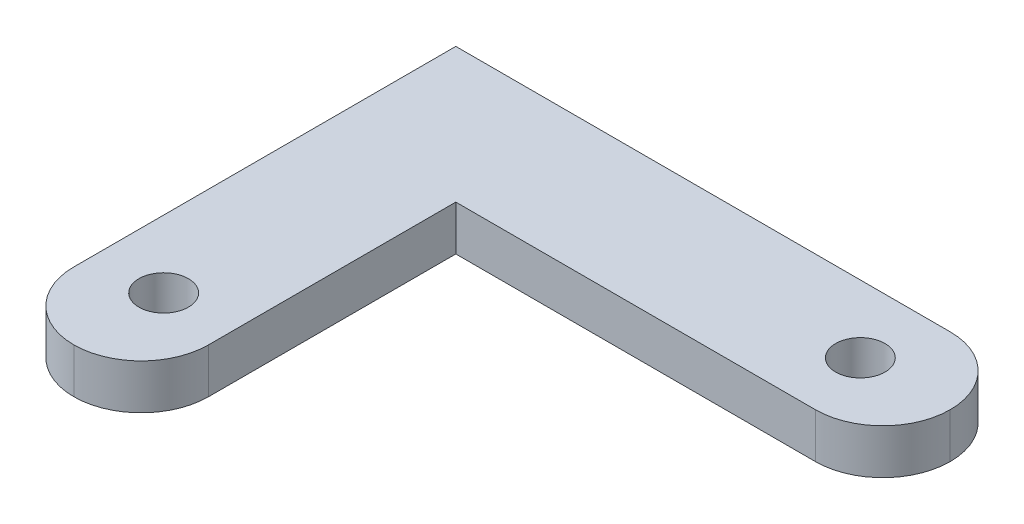
SolidWorks part; units mm, degrees
ref_plane "Front Plane" through (0, 0, 0) normal (0, 0, 1) x (1, 0, 0)
ref_plane "Top Plane" through (0, 0, 0) normal (0, 1, 0) x (1, 0, 0)
ref_plane "Right Plane" through (0, 0, 0) normal (1, 0, 0) x (0, 0, -1)
sketch "Sketch1" plane through (0, 0, 0) normal (0, 1, 0) x (1, 0, 0)
  line L0 (-6, 6) -> (-6, -14)
  line L1 (-6, -14) -> (0, -14)
  line L2 (0, -14) -> (0, 0)
  line L3 (0, 0) -> (19, 0)
  line L4 (19, 0) -> (19, 6)
  line L5 (19, 6) -> (-6, 6)
  point P2 (0, 0)
  dimension "D1" = 14
  dimension "D2" = 20
  dimension "D3" = 6
  dimension "D4" = 25
  dimension "D5" = 6
extrude "Boss-Extrude1" add sketch "Sketch1" along normal blind 2
sketch "Sketch2" plane through (0, 2, 0) normal (0, 1, 0) x (1, 0, 0)
  circle A0 centre (-3, -10) radius 1.1
  circle A1 centre (15, 3) radius 1.1
  point P4 (-5.0135, -14.1374)
  dimension "D5" = 2.2
  dimension "D6" = 2.2
  dimension "D1" = 3
  dimension "D2" = 15
  dimension "D3" = 3
  dimension "D4" = 10
extrude "Cut-Extrude1" cut sketch "Sketch2" against normal blind 2
fillet "Fillet1" radius 3 4 edges at (19, 1, -6) (19, 1, 0) (-6, 1, 14) (0, 1, 14)
